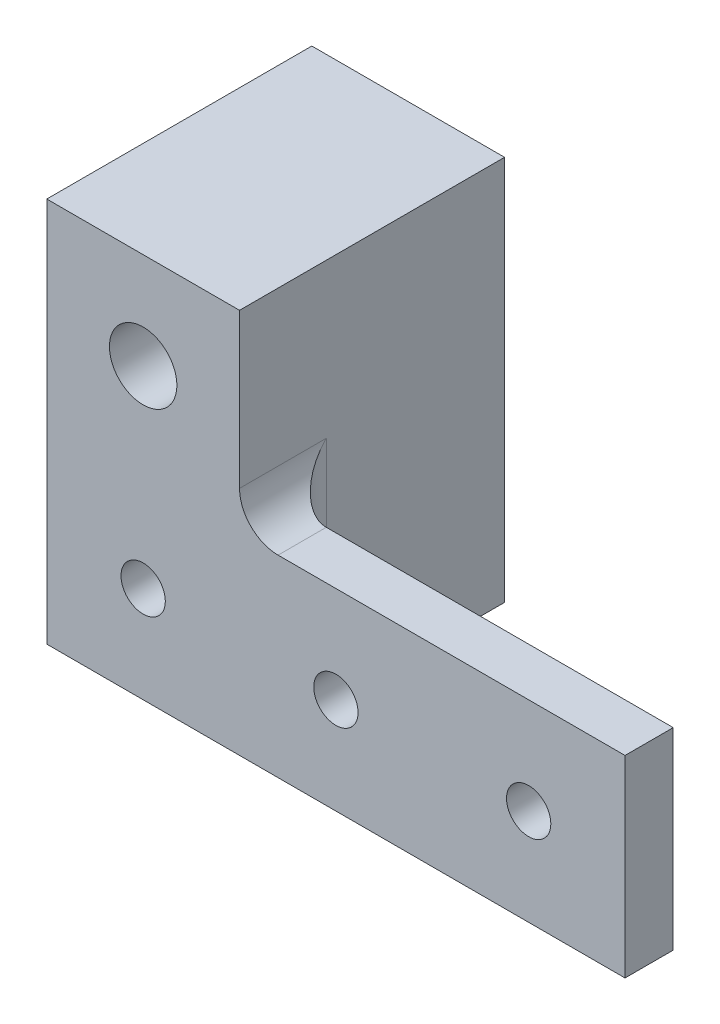
SolidWorks part; units mm, degrees
ref_plane "Front Plane" through (0, 0, 0) normal (0, 0, 1) x (1, 0, 0)
ref_plane "Top Plane" through (0, 0, 0) normal (0, 1, 0) x (1, 0, 0)
ref_plane "Right Plane" through (0, 0, 0) normal (1, 0, 0) x (0, 0, -1)
sketch "Sketch1" plane through (0, 0, 0) normal (0, 0, 1) x (1, 0, 0)
  line L0 (0, 0) -> (0, 50.8)
  line L1 (0, 50.8) -> (25.4, 50.8)
  line L2 (25.4, 50.8) -> (25.4, 25.4)
  line L3 (25.4, 25.4) -> (76.2, 25.4)
  line L4 (76.2, 25.4) -> (76.2, 0)
  line L5 (76.2, 0) -> (0, 0)
  dimension "D1" = 50.8
  dimension "D2" = 25.4
  dimension "3" = 76.2
extrude "Boss-Extrude1" add sketch "Sketch1" along normal blind 34.925
sketch "Sketch2" plane through (0, 0, 34.925) normal (0, 0, 1) x (1, 0, 0)
  line L0 (25.4, 50.8) -> (0, 50.8) construction
  line L1 (25.4, 25.4) -> (25.4, 50.8) construction
  line L2 (0, 0) -> (76.2, 0) construction
  circle A0 centre (12.7, 38.1) radius 2.921
  circle A1 centre (12.7, 12.7) radius 2.921
  circle A2 centre (38.1, 12.7) radius 2.921
  circle A3 centre (63.5, 12.7) radius 2.921
  dimension ".23" = 5.842
  dimension "D2" = 12.7
  dimension "D3" = 12.7
  dimension "D4" = 12.7
  dimension "D5" = 3
extrude "Cut-Extrude1" cut sketch "Sketch2" against normal through all
sketch "Sketch3" plane through (0, 0, 34.925) normal (0, 0, 1) x (1, 0, 0)
  line L0 (25.4, 50.8) -> (0, 50.8) construction
  line L1 (0, 0) -> (4.7625, 0)
  line L2 (0, 0) -> (0, 50.8)
  line L3 (0, 50.8) -> (4.7625, 50.8)
  line L4 (4.7625, 0) -> (4.7625, 50.8)
  dimension "D1" = 4.7625
sketch "Sketch4" plane through (0, 0, 0) normal (0, -1, 0) x (1, 0, 0)
  line L1 (76.2, 0) -> (25.4, 0)
  line L2 (76.2, 0) -> (76.2, 28.575)
  line L3 (76.2, 28.575) -> (25.4, 28.575)
  line L4 (25.4, 0) -> (25.4, 28.575)
  dimension "D1" = 28.575
  dimension "D2" = 50.8
extrude "Cut-Extrude3" cut sketch "Sketch4" against normal through all
fillet "Fillet1" radius 5.08 2 edges at (25.4, 12.7, 28.575) (25.4, 25.4, 31.75)
sketch "Sketch5" plane through (0, 0, 34.925) normal (0, 0, 1) x (1, 0, 0)
  circle A0 centre (12.7, 38.1) radius 4.445
  dimension "0." = 8.89
extrude "Cut-Extrude4" cut sketch "Sketch5" against normal blind 22.225
